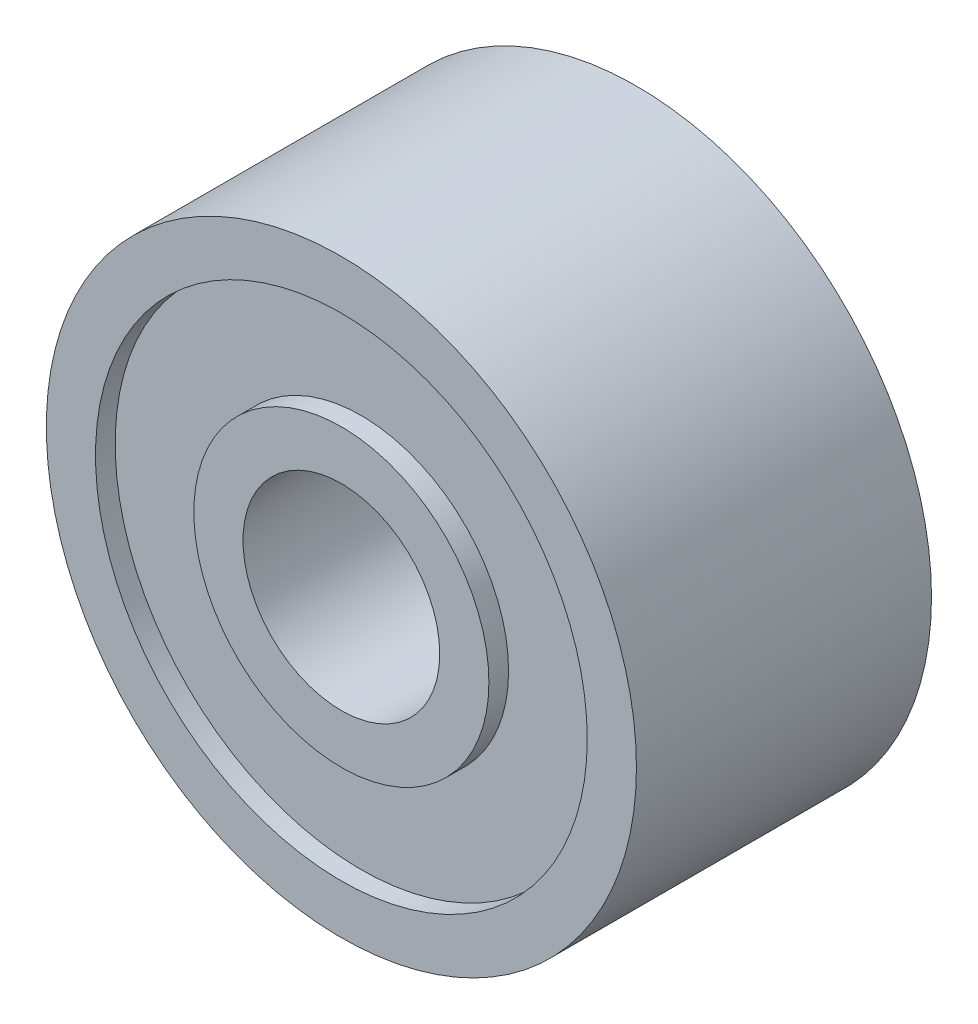
SolidWorks part; units mm, degrees
ref_plane "Front Plane" through (0, 0, 0) normal (0, 0, 1) x (1, 0, 0)
ref_plane "Top Plane" through (0, 0, 0) normal (0, 1, 0) x (1, 0, 0)
ref_plane "Right Plane" through (0, 0, 0) normal (1, 0, 0) x (0, 0, -1)
sketch "Sketch1" plane through (0, 0, 0) normal (0, 0, 1) x (1, 0, 0)
  circle A0 centre (0, 0) radius 3
  circle A1 centre (0, 0) radius 1
  dimension "D1" = 2
  dimension "D2" = 6
extrude "Boss-Extrude1" add sketch "Sketch1" along normal mid plane 3
sketch "Sketch2" plane through (0, 0, 1.5) normal (0, 0, 1) x (1, 0, 0)
  circle A5 centre (0, 0) radius 2.5
  circle A6 centre (0, 0) radius 2.5
  circle A8 centre (0, 0) radius 1.5
  circle A9 centre (0, 0) radius 1.5
  dimension "D1" = 0.5
  dimension "D2" = 0.5
extrude "Cut-Extrude1" cut sketch "Sketch2" against normal blind 0.2
extrude "Cut-Extrude2" cut sketch "Sketch2<2>" along normal blind 0.2 from surface starting at face at (3, 0, -1.5)
sketch "Sketch2<2>" plane through (0, 0, 1.5) normal (0, 0, 1) x (1, 0, 0) same geometry as "Sketch2"
